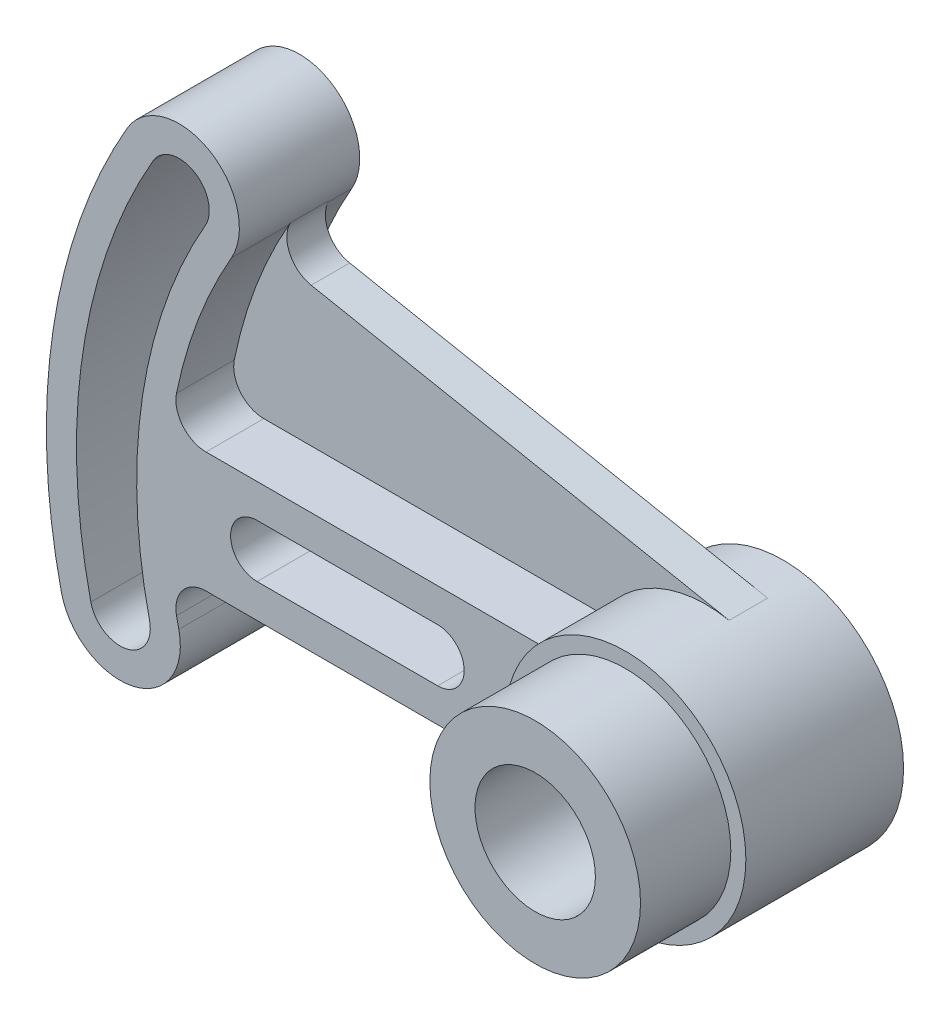
SolidWorks part; units mm, degrees
ref_plane "Front Plane" through (0, 0, 0) normal (0, 0, 1) x (1, 0, 0)
ref_plane "Top Plane" through (0, 0, 0) normal (0, 1, 0) x (1, 0, 0)
ref_plane "Right Plane" through (0, 0, 0) normal (1, 0, 0) x (0, 0, -1)
sketch "Sketch1" plane through (0, 0, 0) normal (0, 0, 1) x (1, 0, 0)
  circle A0 centre (0, 0) radius 25.4
extrude "Boss-Extrude1" add sketch "Sketch1" along normal blind 33.274
sketch "Sketch2" plane through (0, 0, 33.274) normal (0, 0, 1) x (1, 0, 0)
  circle A0 centre (0, 0) radius 22.225
extrude "Boss-Extrude2" add sketch "Sketch2" along normal blind 19.05
sketch "Sketch3" plane through (0, 0, 0) normal (0, 0, 1) x (1, 0, 0)
  circle A0 centre (0, 0) radius 12.7
extrude "Cut-Extrude2" cut sketch "Sketch3" along normal through all
ref_plane "Plane1" through (0, 0, 3.048) normal (0, 0, -1) x (-1, 0, 0)
sketch "Sketch5" plane through (0, 0, 3.048) normal (0, 0, -1) x (-1, 0, 0)
  line L0 (0, 0) -> (55.938, 32.2958) construction
  line L1 (0, -25.4) -> (79.4734, -25.4) construction
  line L2 (21.997, 12.7) -> (100.8031, 12.7)
  line L3 (21.997, -12.7) -> (100.8031, -12.7)
  line L4 (27.94, 0) -> (-27.94, 0) construction
  arc A0 (113.572, -12.8799) -> (111.442, -25.4) centre (0, 0) ccw construction
  arc A1 (109.9852, 63.5) -> (87.9882, 50.8) centre (98.9867, 57.15) ccw
  arc A2 (99.0596, -22.5778) -> (124.142, -25.4) centre (111.442, -25.4) ccw
  arc A3 (109.9852, 63.5) -> (123.8245, -28.2222) centre (0, 0) cw
  arc A4 (87.9882, 50.8) -> (100.8031, 12.7) centre (0, 0) cw
  circle A5 centre (0, 0) radius 25.4 construction
  circle A6 centre (0, 0) radius 25.4
  arc A7 (100.8031, -12.7) -> (99.0596, -22.5778) centre (0, 0) cw
  dimension "D2" = 228.6
  dimension "D1" = 25.4
  dimension "D3" = 25.4
  dimension "D4" = 12.7
extrude "Boss-Extrude3" add sketch "Sketch5" against normal blind 25.4 contours L3 A7 A2 A3 A1 A4 L2 A6 region at (-89.7416, 9.5389, 3.048)
fillet "Fillet1" radius 6.35 1 edges at (-100.8031, 12.7, 15.748)
fillet "Fillet2" radius 6.35 1 edges at (-100.8031, -12.7, 15.748)
sketch "Sketch6" plane through (0, 0, 3.048) normal (0, 0, -1) x (-1, 0, 0)
  line L0 (28.7782, 0) -> (-28.7782, 0) construction
  line L1 (44.45, 5.588) -> (82.55, 5.588)
  line L2 (44.45, -5.588) -> (82.55, -5.588)
  line L5 (21.997, -12.7) -> (93.3256, -12.7)
  line L6 (93.3256, 12.7) -> (21.997, 12.7)
  arc A0 (44.45, 5.588) -> (44.45, -5.588) centre (44.45, 0) ccw
  arc A1 (82.55, -5.588) -> (82.55, 5.588) centre (82.55, 0) ccw
  arc A2 (98.9867, 57.15) -> (111.4298, -25.4538) centre (0, 0) cw construction
  arc A3 (117.6203, -26.8679) -> (104.486, 60.325) centre (0, 0) ccw
  arc A4 (105.2392, -24.0397) -> (93.4874, 53.975) centre (0, 0) ccw
  arc A5 (105.2392, -24.0397) -> (117.6203, -26.8679) centre (111.4298, -25.4538) ccw
  arc A6 (104.486, 60.325) -> (93.4874, 53.975) centre (98.9867, 57.15) ccw
  arc A10 (99.5473, -20.32) -> (93.3256, -12.7) centre (93.3256, -19.05) ccw
  arc A11 (99.0596, -22.5778) -> (99.5473, -20.32) centre (0, 0) ccw
  arc A12 (99.0596, -22.5778) -> (123.8245, -28.2222) centre (111.442, -25.4) ccw
  arc A13 (123.8245, -28.2222) -> (109.9852, 63.5) centre (0, 0) ccw
  arc A14 (109.9852, 63.5) -> (87.9882, 50.8) centre (98.9867, 57.15) ccw
  arc A15 (99.5473, 20.32) -> (87.9882, 50.8) centre (0, 0) ccw
  arc A16 (93.3256, 12.7) -> (99.5473, 20.32) centre (93.3256, 19.05) ccw
  arc A17 (21.997, -12.7) -> (21.997, 12.7) centre (0, 0) ccw
  arc A19 (99.0596, -22.5778) -> (99.5473, -20.32) centre (0, 0) ccw
  point P14 (113.0249, 17.0256)
  dimension "D1" = 11.176
  dimension "D2" = 38.1
  dimension "D3" = 44.45
  dimension "D4" = 0
extrude "Cut-Extrude3" cut sketch "Sketch6" against normal through all contours L2 A1 L1 A0 | A3 A6 A4 A5 region at (-63.5, 0, 3.048) region at (-109.8641, 16.5494, 3.048)
ref_plane "Plane2" through (0, 0, 8.128) normal (0, 0, 1) x (1, 0, 0)
sketch "Sketch7" plane through (0, 0, 8.128) normal (0, 0, 1) x (1, 0, 0)
  line L0 (-21.997, 12.7) -> (-93.3256, 12.7) construction
  line L1 (-21.997, 12.7) -> (-93.3256, 12.7)
  line L2 (-91.7198, 43.7039) -> (4.8465, 24.9333)
  circle A0 centre (0, 0) radius 25.4 construction
  arc A1 (-99.5473, 20.32) -> (-93.3256, 12.7) centre (-93.3256, 19.05) ccw construction
  arc A2 (-87.9882, 50.8) -> (-99.5473, 20.32) centre (0, 0) ccw construction
  circle A3 centre (0, 0) radius 25.4
  arc A4 (-99.5473, 20.32) -> (-93.3256, 12.7) centre (-93.3256, 19.05) ccw
  arc A5 (-87.9882, 50.8) -> (-99.5473, 20.32) centre (0, 0) ccw
extrude "Boss-Extrude4" add sketch "Sketch7" along normal blind 8.128 contours L2 A5 A4 L1 A3 region at (-59.6974, 25.015, 8.128)
fillet "Fillet3" radius 6.35 1 edges at (-91.7198, 43.7039, 12.192)
